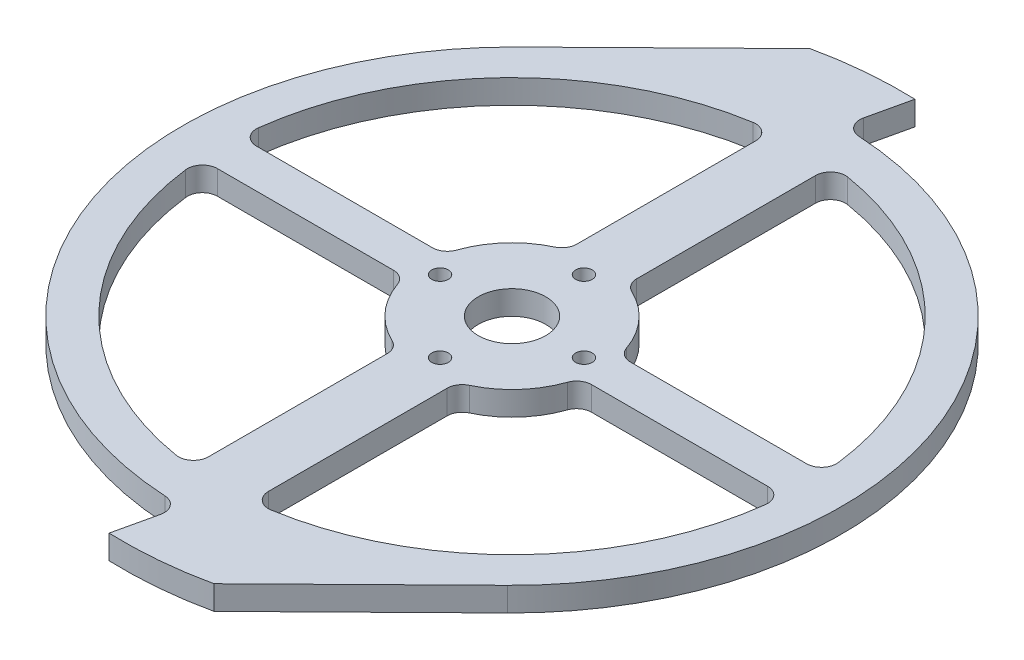
SolidWorks part; units mm, degrees
material "Alloy Steel"
ref_plane "Front Plane" through (0, 0, 0) normal (0, 0, 1) x (1, 0, 0)
ref_plane "Top Plane" through (0, 0, 0) normal (0, 1, 0) x (1, 0, 0)
ref_plane "Right Plane" through (0, 0, 0) normal (1, 0, 0) x (0, 0, -1)
sketch "Sketch1" plane through (0, 0, 0) normal (0, 1, 0) x (1, 0, 0)
  line L0 (-6.35, 17.9605) -> (-6.35, 61.586)
  line L1 (6.35, 17.9605) -> (6.35, 61.586)
  line L2 (-6.35, -17.9605) -> (-6.35, -61.586)
  line L3 (6.35, -17.9605) -> (6.35, -61.586)
  line L4 (2.881, 82.4997) -> (0, 69.85)
  line L5 (-2.881, -82.4997) -> (0, -69.85)
  line L6 (-17.5153, 80.6704) -> (0, 0) construction
  line L7 (-17.5153, 80.6704) -> (-48.9187, 49.8596)
  line L8 (-61.9125, 0) -> (61.9125, 0) construction
  line L9 (61.7748, 4.1275) -> (-61.7748, 4.1275)
  line L10 (61.7748, -4.1275) -> (-61.7748, -4.1275)
  line L11 (2.881, 82.4997) -> (0, 0) construction
  line L12 (0, 61.9125) -> (0, 19.05) construction
  line L13 (17.5153, -80.6704) -> (48.9187, -49.8596)
  circle A0 centre (0, 0) radius 69.85
  circle A1 centre (0, 0) radius 61.9125
  circle A2 centre (0, 0) radius 19.05
  arc A3 (2.881, 82.4997) -> (-17.5153, 80.6704) centre (0, 0) ccw
  arc A4 (-2.881, -82.4997) -> (17.5153, -80.6704) centre (0, 0) ccw
  point P21 (0, 0)
  point P29 (0, 0)
  point P42 (0, 0)
  dimension "D1" = 139.7
  dimension "D2" = 123.825
  dimension "D3" = 38.1
  dimension "D8" = 2
  dimension "D9" = 2
  dimension "D4" = 12.7
  dimension "D6" = 82.55
  dimension "D7" = 8.255
  dimension "D10" = 12.25
  dimension "D5" = 2
extrude "Boss-Extrude1" add sketch "Sketch1" along normal blind 5.08 contours A0 A1 | A2 L2 A1 L3 | A0 | A2 L10 | A2 L9 A1 L10 | L10 A2 L9 | L9 A2 | A2 L10 A1 L9 | A2 L1 A1 L0 | A0 A3 region at (0, 0, -40.2463) region at (0, 0, -10.3572) region at (-40.3831, 0, 0) region at (0, 0, 0) region at (40.3831, 0, 0) region at (0, 0, 10.3572) region at (0, 0, 40.2463) region at (-14.7637, 0, -73.0133) region at (47.9944, 0, -47.9944) region at (14.7637, 0, 73.0133)
sketch "Sketch2" plane through (0, 5.08, 0) normal (0, 1, 0) x (1, 0, 0)
  circle A0 centre (0, 0) radius 7.1438
  circle A1 centre (-15.24, 0) radius 1.7526
  circle A2 centre (0, 15.24) radius 1.7526
  circle A3 centre (15.24, 0) radius 1.7526
  circle A4 centre (0, -15.24) radius 1.7526
  point P14 (0, 0)
  dimension "D1" = 14.2875
  dimension "D2" = 3.5052
  dimension "D3" = 15.24
  dimension "D4" = 4
extrude "Cut-Extrude1" cut sketch "Sketch2" against normal blind 6.35
fillet "Fillet1" radius 3.175 2 edges at (0, 2.54, 69.85) (0, 2.54, -69.85)
fillet "Fillet2" radius 3.175 16 edges at (-6.35, 2.54, 61.586) (18.5975, 2.54, 4.1275) (-61.7748, 2.54, 4.1275) (6.35, 2.54, 17.9605) (-18.5975, 2.54, 4.1275) (-6.35, 2.54, 17.9605) (-6.35, 2.54, -61.586) (61.7748, 2.54, 4.1275) (6.35, 2.54, 61.586) (-61.7748, 2.54, -4.1275) (18.5975, 2.54, -4.1275) (6.35, 2.54, -17.9605) (-18.5975, 2.54, -4.1275) (-6.35, 2.54, -17.9605) (61.7748, 2.54, -4.1275) (6.35, 2.54, -61.586)
